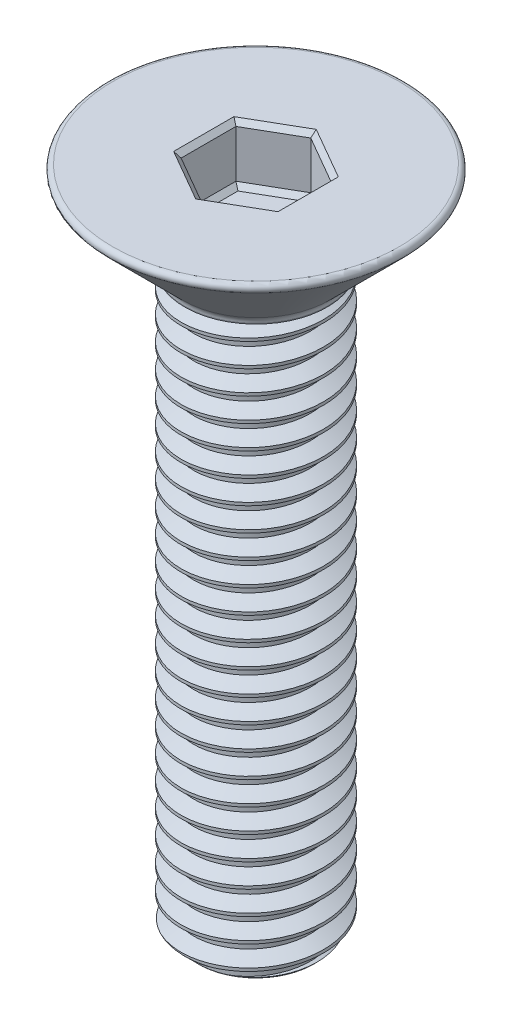
SolidWorks part; units mm, degrees
material "AISI Type A2 Tool Steel"
ref_plane "Front Plane" through (0, 0, 0) normal (0, 0, 1) x (1, 0, 0)
ref_plane "Top Plane" through (0, 0, 0) normal (0, 1, 0) x (1, 0, 0)
ref_plane "Right Plane" through (0, 0, 0) normal (1, 0, 0) x (0, 0, -1)
sketch "Sketch1" plane through (0, 0, 0) normal (0, 1, 0) x (1, 0, 0)
  circle A0 centre (0, 0) radius 1.5
  dimension "D1" = 3
extrude "Boss-Extrude1" add sketch "Sketch1" along normal blind 12.14
thread "Thread1" pitch 0.5 method cut profile "Thread Profile1" start angle 0, offset 1, length 0, pitch 0.5, diameter 3
ref_plane "Plane1" through (-1.5, 13.14, 0) normal (0, 0, 1) x (-1, 0, 0)
sketch "Thread Profile1" plane through (-1.5, 13.14, 0) normal (0, 0, 1) x (-1, 0, 0)
  line L0 (0, 0) -> (0, 0.5) construction
  line L11 (0, 0) -> (0, 0.4375)
  line L12 (0, 0.4375) -> (-0.2706, 0.2812)
  line L13 (-0.2706, 0.2812) -> (-0.2706, 0.1562)
  line L15 (-0.2706, 0.1562) -> (0, 0)
  line L17 (-0.2706, 0.2187) -> (0, 0.2187) construction
  point P2 (0, 0)
  dimension "Pitch" = 0.5
  dimension "Profile_Angle" = 60
  dimension "Profile_Land" = 0.125
  dimension "Profile_Height" = 0.2706
sketch "Sketch5" plane through (0, 12.14, 0) normal (0, 1, 0) x (1, 0, 0)
  circle A0 centre (0, 0) radius 1.5
  dimension "D1" = 3
extrude "Boss-Extrude2" add sketch "Sketch5" along normal blind 0.1
sketch "Sketch6" plane through (0, 12.24, 0) normal (0, 1, 0) x (1, 0, 0)
  circle A0 centre (0, 0) radius 1.5
  dimension "D1" = 3
extrude "Boss-Extrude3" add sketch "Sketch6" along normal blind 1.76 draft 45 draft outward yes
sketch "Sketch7" plane through (0, 0, 0) normal (0, 0, 1) x (1, 0, 0)
  line L0 (0, 0) -> (0, 0.1997) construction
  line L1 (0, 0) -> (1.51, 0) construction
  line L2 (1.51, 0) -> (1.51, 0.3)
  line L3 (1.51, 0.3) -> (1.21, 0)
  line L4 (1.21, 0) -> (1.51, 0)
  dimension "D1" = 45
  dimension "D2" = 0.3
  dimension "D3" = 1.51
revolve "Cut-Revolve1" cut sketch "Sketch7" angle 360 about L0
fillet "Fillet1" radius 0.1 1 edges at (0, 14, 3.26)
fillet "Fillet2" radius 0.2 1 edges at (0, 12.24, 1.5)
sketch "Sketch8" plane through (0, 14, 0) normal (0, 1, 0) x (1, 0, 0)
  line L1 (0, 1.1547) -> (-1, 0.5774)
  line L2 (-1, 0.5774) -> (-1, -0.5774)
  line L3 (-1, -0.5774) -> (0, -1.1547)
  line L4 (0, -1.1547) -> (1, -0.5774)
  line L5 (1, -0.5774) -> (1, 0.5774)
  line L6 (1, 0.5774) -> (0, 1.1547)
  circle A0 centre (0, 0) radius 1 construction
  dimension "D1" = 2
extrude "Cut-Extrude1" cut sketch "Sketch8" against normal blind 1.1
chamfer "Chamfer1" distance 0.1 angle 45 6 edges at (-1, 14, 0) (-0.5, 14, 0.866) (0.5, 14, 0.866) (1, 14, 0) (0.5, 14, -0.866) (-0.5, 14, -0.866)
sketch "Sketch9" plane through (0, 12.9, 0) normal (0, 1, 0) x (1, 0, 0)
  line L1 (0, 1.1547) -> (-1, 0.5774)
  line L2 (-1, 0.5774) -> (-1, -0.5774)
  line L3 (-1, -0.5774) -> (0, -1.1547)
  line L4 (0, -1.1547) -> (1, -0.5774)
  line L5 (1, -0.5774) -> (1, 0.5774)
  line L6 (1, 0.5774) -> (0, 1.1547)
  circle A0 centre (0, 0) radius 1 construction
extrude "Cut-Extrude2" cut sketch "Sketch9" against normal blind 0.1 draft 45
